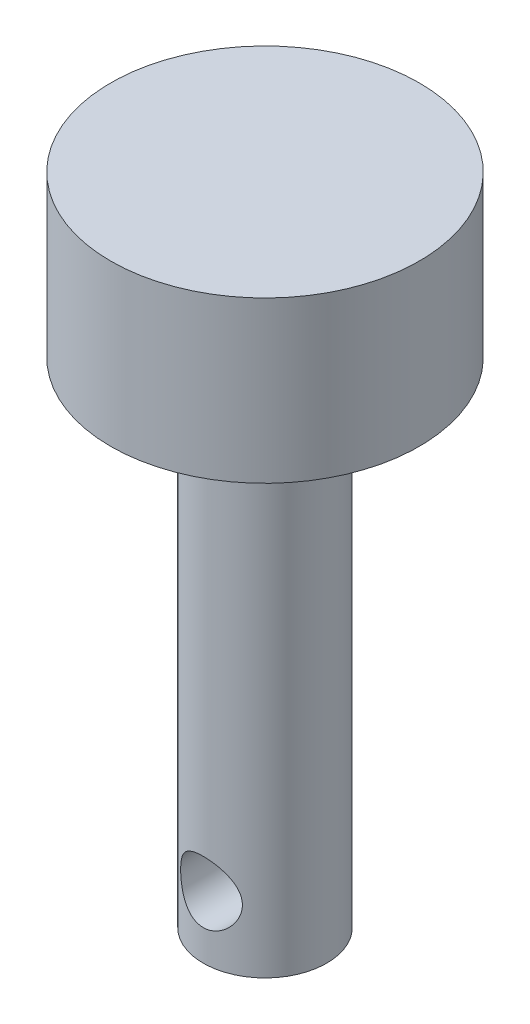
SolidWorks part; units mm, degrees
ref_plane "Front Plane" through (0, 0, 0) normal (0, 0, 1) x (1, 0, 0)
ref_plane "Top Plane" through (0, 0, 0) normal (0, 1, 0) x (1, 0, 0)
ref_plane "Right Plane" through (0, 0, 0) normal (1, 0, 0) x (0, 0, -1)
sketch "Sketch1" plane through (0, 0, 0) normal (0, 0, 1) x (1, 0, 0)
  line L0 (0, 0) -> (0, 53)
  line L1 (0, 53) -> (12.5, 53)
  line L2 (12.5, 53) -> (12.5, 40)
  line L3 (12.5, 40) -> (5, 40)
  line L4 (5, 0) -> (0, 0)
  line L5 (5, 0) -> (5, 40)
  dimension "D1" = 40
  dimension "D2" = 13
  dimension "D3" = 12.5
  dimension "D4" = 5
revolve "Revolve1" add sketch "Sketch1" angle 360 about L0
sketch "Sketch2" plane through (0, 0, 0) normal (0, 0, 1) x (1, 0, 0)
  circle A0 centre (0, 5) radius 2.5
  point P2 (0, 0)
  point P4 (0, 6.1518)
  dimension "D1" = 5
  dimension "D2" = 5
extrude "Cut-Extrude1" cut sketch "Sketch2" against normal blind 10 and the other way blind 10
